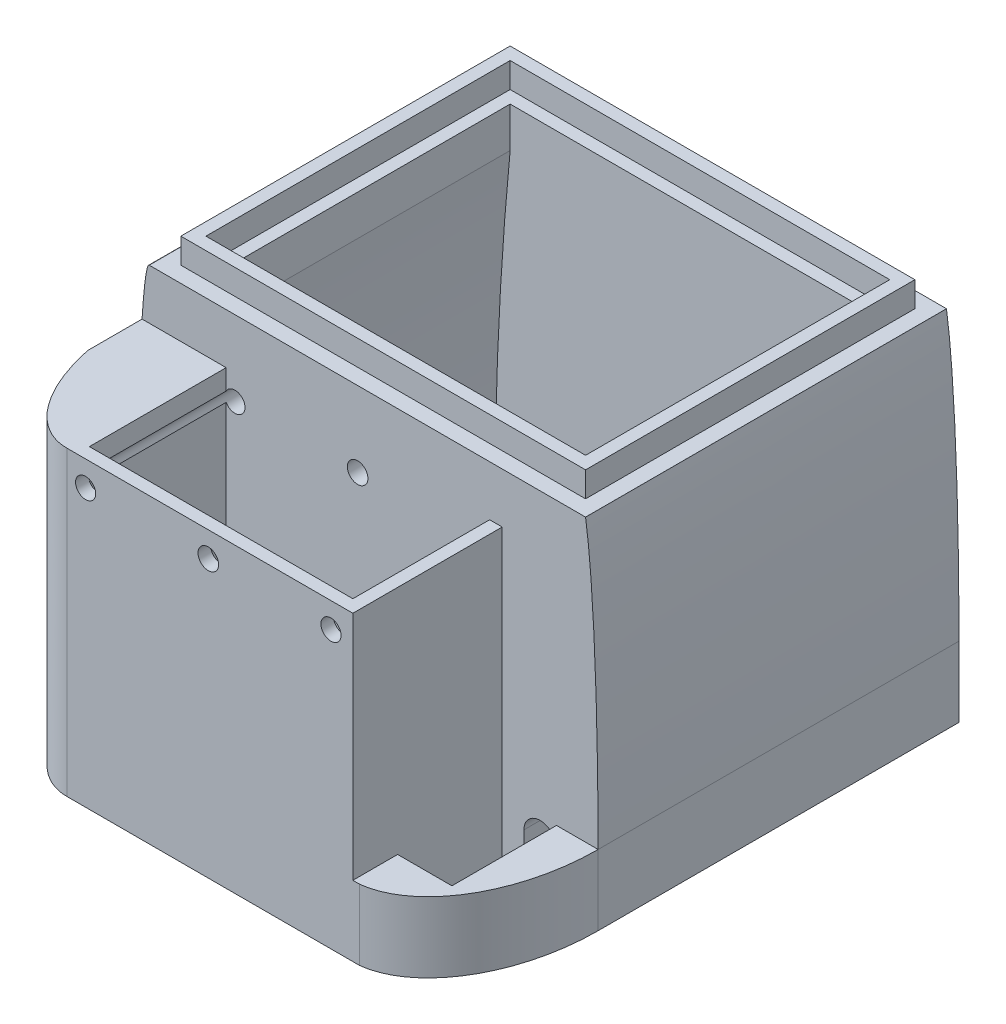
SolidWorks part; units mm, degrees
ref_plane "Front Plane" through (0, 0, 0) normal (0, 0, 1) x (1, 0, 0)
ref_plane "Top Plane" through (0, 0, 0) normal (0, 1, 0) x (1, 0, 0)
ref_plane "Right Plane" through (0, 0, 0) normal (1, 0, 0) x (0, 0, -1)
sketch "Sketch3" plane through (0, 0, 0) normal (0, 1, 0) x (1, 0, 0)
  line L1 (34.2515, 0) -> (-20.8538, 0)
  line L2 (34.2515, 0) -> (34.2515, -45.5803)
  line L3 (34.2515, -45.5803) -> (-20.8538, -45.5803)
  line L4 (-20.8538, 0) -> (-20.8538, -45.5803)
  dimension "D1" = 55.1053
  dimension "D2" = 45.5803
extrude "Boss-Extrude2" add sketch "Sketch3" along normal blind 44.45
sketch "Sketch11" plane through (0, 44.45, 0) normal (0, 1, 0) x (1, 0, 0)
  line L4 (30.6701, -3.5814) -> (-17.2724, -3.5814)
  line L5 (-17.2724, -3.5814) -> (-17.2724, -41.9989)
  line L6 (-17.2724, -41.9989) -> (30.6701, -41.9989)
  line L7 (30.6701, -41.9989) -> (30.6701, -3.5814)
  line L8 (32.2576, -43.5864) -> (32.2576, -1.9939)
  line L9 (32.2576, -1.9939) -> (-18.8599, -1.9939)
  line L10 (-18.8599, -1.9939) -> (-18.8599, -43.5864)
  line L11 (-18.8599, -43.5864) -> (32.2576, -43.5864)
  line L12 (32.2576, -43.5864) -> (32.2576, -1.9939)
  line L13 (32.2576, -1.9939) -> (-18.8599, -1.9939)
  line L14 (-18.8599, -1.9939) -> (-18.8599, -43.5864)
  line L15 (-18.8599, -43.5864) -> (32.2576, -43.5864)
  dimension "D1" = 1.9939
  dimension "D2" = 1.5875
extrude "Boss-Extrude3" add sketch "Sketch11" along normal blind 3.175
sketch "Sketch13" plane through (0, 44.45, 0) normal (0, 1, 0) x (1, 0, 0)
  line L8 (-15.6849, -40.4114) -> (29.0826, -40.4114)
  line L9 (29.0826, -40.4114) -> (29.0826, -5.1689)
  line L10 (29.0826, -5.1689) -> (-15.6849, -5.1689)
  line L11 (-15.6849, -5.1689) -> (-15.6849, -40.4114)
  line L12 (-15.6849, -40.4114) -> (29.0826, -40.4114)
  line L13 (29.0826, -40.4114) -> (29.0826, -5.1689)
  line L14 (29.0826, -5.1689) -> (-15.6849, -5.1689)
  line L15 (-15.6849, -5.1689) -> (-15.6849, -40.4114)
  dimension "D1" = 1.5875
extrude "Cut-Extrude3" cut sketch "Sketch13" against normal through all
sketch "Sketch14" plane through (0, 0, 45.5803) normal (0, 0, 1) x (1, 0, 0)
  line L0 (6.6989, 44.45) -> (6.6989, 0) construction
  line L1 (-18.8599, 44.45) -> (32.2576, 44.45) construction
  line L2 (-20.8538, 0) -> (34.2515, 0) construction
  line L3 (-2.8261, 6.35) -> (-2.8261, 0)
  line L4 (-2.8261, 0) -> (3.5239, 0)
  line L5 (3.5239, 0) -> (3.5239, 6.35)
  line L6 (9.8739, 6.35) -> (9.8739, 0)
  line L7 (9.8739, 0) -> (16.2239, 0)
  line L8 (16.2239, 0) -> (16.2239, 6.35)
  line L9 (26.4653, 0) -> (30.5812, 0)
  line L10 (30.5812, 0) -> (30.5812, 6.35)
  line L12 (26.4653, 0) -> (26.4653, 6.35)
  arc A0 (3.5239, 6.35) -> (-2.8261, 6.35) centre (0.3489, 6.35) ccw
  arc A1 (16.2239, 6.35) -> (9.8739, 6.35) centre (13.0489, 6.35) ccw
  arc A2 (26.4653, 6.35) -> (30.5812, 6.35) centre (28.5233, 6.35) cw
  dimension "D1" = 6.35
  dimension "D3" = 6.35
  dimension "D2" = 6.35
  dimension "D4" = 6.35
  dimension "D5" = 6.35
extrude "Cut-Extrude4" cut sketch "Sketch14" against normal up to vertex (5.1689 mm away) up to point (29.0826, 0, 40.4114)
sketch "Sketch19" plane through (0, 0, 0) normal (0, -1, 0) x (1, 0, 0)
  line L0 (-20.8538, 45.5803) -> (-22.4413, 45.5803)
  line L1 (-22.4413, 45.5803) -> (-22.4413, 0)
  line L2 (-22.4413, 0) -> (-20.8538, 0)
  line L3 (-20.8538, 0) -> (-20.8538, 45.5803)
  line L4 (34.2515, 45.5803) -> (35.839, 45.5803)
  line L5 (35.839, 45.5803) -> (35.839, 0)
  line L6 (35.839, 0) -> (34.2515, 0)
  line L7 (34.2515, 0) -> (34.2515, 45.5803)
  dimension "D1" = 1.5875
  dimension "D2" = 1.5875
extrude "Boss-Extrude4" add sketch "Sketch19" against normal blind 44.45
sketch "Sketch21" plane through (0, 0, 0) normal (0, -1, 0) x (-1, 0, 0)
  line L0 (15.6849, -40.4114) -> (17.5899, -40.4114)
  line L1 (17.5899, -40.4114) -> (17.5899, -5.1689)
  line L2 (17.5899, -5.1689) -> (15.6849, -5.1689)
  line L3 (15.6849, -5.1689) -> (15.6849, -40.4114)
  line L4 (-30.9876, -40.4114) -> (-29.0826, -40.4114)
  line L5 (-30.9876, -40.4114) -> (-30.9876, -5.1689)
  line L6 (-29.0826, -40.4114) -> (-29.0826, -5.1689)
  line L7 (-29.0826, -5.1689) -> (-30.9876, -5.1689)
  dimension "D1" = 1.905
  dimension "D2" = 1.905
extrude "Cut-Extrude5" cut sketch "Sketch21" against normal blind 39.37
fillet "Fillet1" radius 406.4 1 edges at (-17.5899, 39.37, 22.7901)
fillet "Fillet2" radius 406.4 1 edges at (30.9876, 39.37, 22.7901)
sketch "Sketch22" plane through (0, 0, 0) normal (0, -1, 0) x (1, 0, 0)
  circle A0 centre (-19.6473, 42.7863) radius 1.524
  circle A1 centre (33.045, 42.7863) radius 1.524
  circle A2 centre (-19.6473, 2.794) radius 1.524
  circle A3 centre (33.045, 2.794) radius 1.524
  dimension "D3" = 3.048
  dimension "D6" = 3.048
  dimension "D9" = 3.048
  dimension "D12" = 3.048
extrude "Cut-Extrude7" cut sketch "Sketch22" against normal blind 3.175
sketch "Sketch23" plane through (0, 0, 0) normal (0, -1, 0) x (1, 0, 0)
  line L0 (22.1357, 64.4398) -> (21.3799, 64.4398)
  line L1 (-11.1383, 45.5803) -> (-22.4413, 45.5803)
  line L3 (-12.4083, 64.4398) -> (22.1357, 64.4398)
  line L4 (22.1357, 64.4398) -> (22.1357, 62.8523)
  line L11 (-11.1383, 62.8523) -> (22.1357, 62.8523)
  line L15 (-11.1383, 58.1701) -> (-11.1383, 45.5803)
  line L16 (-11.1383, 45.5803) -> (-11.1383, 62.8523)
  ellipse E0 centre (-12.4083, 45.5803) end of major axis (-12.4083, 64.4398) minor radius 10.033 (-12.4083, 64.4398) -> (-22.4413, 45.5803) ccw
  dimension "D1" = 11.303
  dimension "D2" = 34.544
  dimension "D3" = 33.274
  dimension "D5" = 1.5875
extrude "Boss-Extrude5" add sketch "Sketch23" against normal blind 38.1
sketch "Sketch39" plane through (0, 0, 64.4398) normal (0, 0, 1) x (1, 0, 0)
  circle A0 centre (5.467, 34.925) radius 1.2969
  circle A1 centre (-10.027, 34.925) radius 1.27
  circle A2 centre (20.961, 34.925) radius 1.27
  dimension "D2" = 15.494
  dimension "D5" = 2.54
  dimension "D6" = 2.54
  dimension "D1" = 15.494
extrude "Cut-Extrude14" cut sketch "Sketch39" against normal blind 25.4
sketch "Sketch43" plane through (0, 0, 0) normal (0, -1, 0) x (1, 0, 0)
  line L0 (30.5812, 45.5803) -> (35.839, 45.5803)
  line L1 (22.1357, 64.4398) -> (24.536, 64.4398)
  line L2 (22.1357, 64.4398) -> (22.1357, 45.5803)
  line L3 (23.7232, 58.7883) -> (23.7232, 45.5803)
  line L4 (30.5812, 45.5803) -> (30.5812, 58.7883)
  line L6 (23.7232, 58.7883) -> (30.5812, 58.7883)
  line L8 (22.1357, 45.5803) -> (23.7232, 45.5803)
  line L9 (16.2239, 45.5803) -> (26.4653, 45.5803) construction
  ellipse E0 centre (23.7232, 45.5803) end of major axis (23.7232, 64.4824) minor radius 12.1158 (35.839, 45.5803) -> (24.536, 64.4398) ccw
  dimension "D1" = 6.858
  dimension "D2" = 13.208
  dimension "D3" = 1.5875
  dimension "D4" = 11.303
extrude "Boss-Extrude22" add sketch "Sketch43" against normal blind 8.89
sketch "Sketch48" plane through (22.1357, 0, 0) normal (1, 0, 0) x (0, 0, -1)
  line L0 (-64.4398, 38.1) -> (-45.5803, 38.1)
  line L1 (-45.5803, 38.1) -> (-45.5803, 8.89)
  line L4 (-45.5803, 8.89) -> (-64.4398, 8.89)
  line L5 (-64.4398, 8.89) -> (-64.4398, 38.1)
sketch "Sketch51" plane through (0, 0, 64.4398) normal (0, 0, 1) x (1, 0, 0)
  line L1 (-22.4413, 44.45) -> (35.839, 44.45) construction
  line L2 (32.2576, 44.45) -> (34.2515, 44.45)
  line L4 (-22.4413, 38.1) -> (-22.4413, 0) construction
  line L5 (-20.8538, 44.45) -> (-20.8538, 45.621)
  line L6 (34.2515, 44.45) -> (34.2515, 45.621)
  line L7 (34.2515, 44.45) -> (34.2515, 44.4393)
  line L8 (30.5812, 8.89) -> (35.839, 8.89) construction
  line L9 (34.2515, 45.621) -> (37.5559, 45.621)
  line L10 (-20.8538, 45.621) -> (-23.7288, 45.621)
  line L11 (-23.7288, 45.621) -> (-23.7288, 8.89)
  line L12 (-23.7288, 8.89) -> (-22.4413, 8.89)
  line L13 (37.5559, 45.621) -> (37.5559, 8.89)
  line L14 (37.5559, 8.89) -> (35.839, 8.89)
  ellipse E0 centre (-20.8538, 8.89) end of major axis (-20.8538, -26.67) minor radius 1.5875 (-20.8538, 44.45) -> (-22.4413, 8.89) ccw
  ellipse E1 centre (33.2101, 8.89) end of major axis (33.2101, 47.6067) minor radius 2.6289 (35.839, 8.89) -> (34.2515, 44.4393) ccw
  dimension "D2" = 1.9939
extrude "Cut-Extrude15" cut sketch "Sketch51" against normal through all contours E0 L5 L10 L11 L12 | E1 L14 L13 L9 L6 L7
extrude "Boss-Extrude23" add sketch "Sketch48" along normal blind 1.5875
sketch "Sketch52" plane through (0, 0, 64.4398) normal (0, 0, 1) x (1, 0, 0)
  circle A0 centre (20.961, 34.925) radius 1.27
extrude "Cut-Extrude16" cut sketch "Sketch52" against normal blind 25.4
